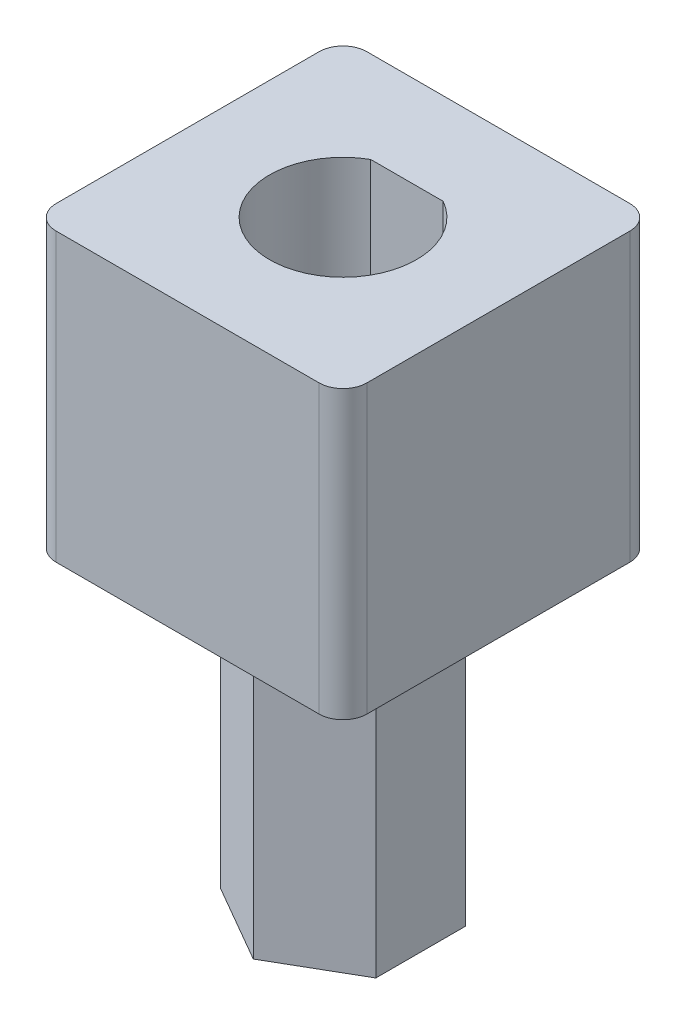
SolidWorks part; units mm, degrees
ref_plane "Front Plane" through (0, 0, 0) normal (0, 0, 1) x (1, 0, 0)
ref_plane "Top Plane" through (0, 0, 0) normal (0, 1, 0) x (1, 0, 0)
ref_plane "Right Plane" through (0, 0, 0) normal (1, 0, 0) x (0, 0, -1)
sketch "Sketch1" plane through (0, 0, 0) normal (0, 1, 0) x (1, 0, 0)
  line L1 (0, -3.7528) -> (3.25, -1.8764)
  line L2 (3.25, -1.8764) -> (3.25, 1.8764)
  line L3 (3.25, 1.8764) -> (0, 3.7528)
  line L4 (0, 3.7528) -> (-3.25, 1.8764)
  line L5 (-3.25, 1.8764) -> (-3.25, -1.8764)
  line L6 (-3.25, -1.8764) -> (0, -3.7528)
  circle A0 centre (0, 0) radius 3.25 construction
  circle A1 centre (0, 0) radius 1.425
  dimension "D2" = 2.85
  dimension "D1" = 6.5
extrude "Boss-Extrude1" add sketch "Sketch1" along normal blind 13
sketch "Sketch2" plane through (0, 13, 0) normal (0, 1, 0) x (1, 0, 0)
  line L1 (-6.5, 6.5) -> (6.5, 6.5)
  line L2 (-6.5, 6.5) -> (-6.5, -6.5)
  line L3 (-6.5, -6.5) -> (6.5, -6.5)
  line L4 (6.5, 6.5) -> (6.5, -6.5)
  circle A0 centre (0, 0) radius 3.075
  point P8 (-6.5, 0)
  point P9 (0, -6.5)
  dimension "D1" = 6.15
  dimension "D2" = 6.5
  dimension "D3" = 6.5
extrude "Boss-Extrude2" add sketch "Sketch2" along normal blind 12
sketch "Sketch3" plane through (0, 25, 0) normal (0, 1, 0) x (1, 0, 0)
  line L0 (-1.5166, 2.675) -> (1.5166, 2.675)
  circle A0 centre (0, 0) radius 3.075 construction
  arc A2 (1.5166, 2.675) -> (-1.5166, 2.675) centre (0, 0) ccw
  circle A3 centre (0, 0) radius 3.075 construction
  point P6 (0, 3.075)
  dimension "D1" = 0.4
extrude "Boss-Extrude3" add sketch "Sketch3" against normal up to next
sketch "Sketch5" plane through (0, 0, -2.675) normal (0, 0, 1) x (1, 0, 0)
  circle A0 centre (0, 20) radius 1.425
  point P3 (0, 0)
  dimension "D1" = 2.85
  dimension "D2" = 20
extrude "Cut-Extrude1" cut sketch "Sketch5" against normal blind 12
fillet "Fillet2" radius 1 4 edges at (6.5, 19, 6.5) (-6.5, 19, 6.5) (6.5, 19, -6.5) (-6.5, 19, -6.5)
sketch "Sketch8" plane through (0, 0, 0) normal (1, 0, 0) x (0, 0, -1)
  line L0 (0, -1000) -> (0, 49000) construction
  line L1 (0, 13) -> (-3.7528, 13)
  line L2 (-3.7528, 13) -> (-6.2528, 13)
  line L3 (-6.2528, 13) -> (-3.7528, 11)
  line L4 (-3.7528, 11) -> (0, 11)
  line L5 (0, 11) -> (0, 13)
  line L6 (-6.5, 13) -> (-5.5, 13) construction
  line L7 (-3.7528, 13) -> (-3.7528, 0) construction
  dimension "D1" = 2
  dimension "D2" = 2.5
revolve "Revolve1" add sketch "Sketch8" angle 360 about L0
